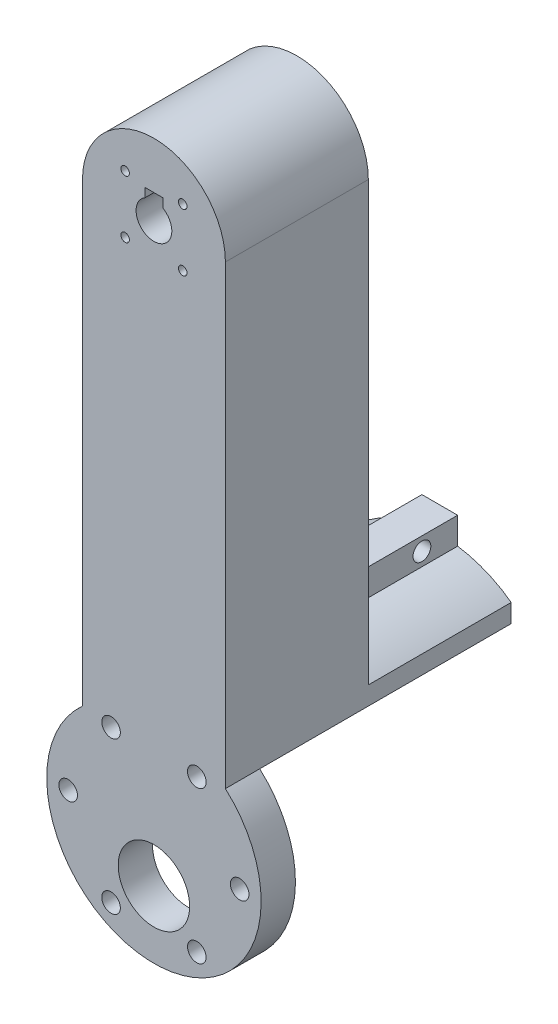
SolidWorks part; units mm, degrees
ref_plane "Front Plane" through (0, 0, 0) normal (0, 0, 1) x (1, 0, 0)
ref_plane "Top Plane" through (0, 0, 0) normal (0, 1, 0) x (1, 0, 0)
ref_plane "Right Plane" through (0, 0, 0) normal (1, 0, 0) x (0, 0, -1)
sketch "Sketch1" plane through (0, 0, 0) normal (0, 0, 1) x (1, 0, 0)
  line L0 (-5.1187, 55.9187) -> (5.1187, 45.6813) construction
  line L2 (12.7, 50.8) -> (12.7, -50.8)
  line L4 (-12.7, 50.8) -> (-12.7, -50.8)
  line L5 (12.7, 50.8) -> (-12.7, -50.8) construction
  line L6 (12.7, -50.8) -> (-12.7, 50.8) construction
  line L7 (5.1187, 55.9187) -> (-5.1187, 45.6813) construction
  line L8 (0, 50.8) -> (0, 51.7208) construction
  arc A0 (-12.7, 50.8) -> (12.7, 50.8) centre (0, 50.8) cw
  arc A1 (12.7, -50.8) -> (-12.7, -50.8) centre (0, -50.8) cw
  circle A2 centre (0, 50.8) radius 3.175
  circle A3 centre (-5.1187, 55.9187) radius 0.762
  circle A4 centre (5.1187, 55.9187) radius 0.762
  circle A5 centre (5.1187, 45.6813) radius 0.762
  circle A6 centre (-5.1187, 45.6813) radius 0.762
  point P0 (0, 0)
  point P14 (0, 50.8)
  point P15 (0, 50.8)
  point P20 (0, 0)
  point P21 (0, 51.7208)
  dimension "D3" = 6.35
  dimension "D6" = 1.524
  dimension "D1" = 25.4
  dimension "D2" = 101.6
  dimension "D4" = 45
  dimension "D5" = 14.478
extrude "Boss-Extrude1" add sketch "Sketch1" along normal blind 25.4
sketch "Sketch2" plane through (0, 0, 0) normal (0, 0, -1) x (-1, 0, 0)
  circle A0 centre (0, -44.45) radius 19.05
  arc A2 (-12.7, -50.8) -> (12.7, -50.8) centre (0, -50.8) ccw construction
  point P5 (0, 0)
  dimension "D1" = 38.1
extrude "Boss-Extrude2" add sketch "Sketch2" against normal blind 25.4
sketch "Sketch4" plane through (0, 0, 25.4) normal (0, 0, 1) x (1, 0, 0)
  circle A0 centre (0, -44.45) radius 19.05
  arc A1 (-12.7, -30.251) -> (12.7, -30.251) centre (0, -44.45) ccw construction
  point P5 (0, 0)
  point P6 (0, 0)
  point P7 (0, 0)
  point P8 (0, 0)
  point P9 (0, 0)
  dimension "D1" = 38.1
sketch "Sketch3" plane through (0, 0, 25.4) normal (0, 0, 1) x (1, 0, 0)
  line L0 (-15.24, -44.45) -> (15.24, -44.45) construction
  line L1 (15.24, -44.45) -> (7.62, -30.9593) construction
  line L2 (-15.24, -44.45) -> (-7.62, -30.9593) construction
  line L3 (-15.24, -44.45) -> (-7.62, -57.9407) construction
  line L4 (15.24, -44.45) -> (7.62, -57.9407) construction
  circle A0 centre (-7.62, -30.9593) radius 1.651
  circle A1 centre (7.62, -30.9593) radius 1.651
  circle A2 centre (-15.24, -44.45) radius 1.651
  circle A3 centre (-7.62, -57.9407) radius 1.651
  circle A4 centre (7.62, -57.9407) radius 1.651
  circle A5 centre (15.24, -44.45) radius 1.651
  point P10 (0, -44.45)
  dimension "D5" = 3.302
  dimension "D1" = 30.48
  dimension "D2" = 15.494
  dimension "D3" = 30.988
  dimension "D4" = 15.24
extrude "Cut-Extrude1" cut sketch "Sketch3" against normal blind 25.4
sketch "Sketch5" plane through (0, 0, 25.4) normal (0, 0, 1) x (1, 0, 0)
  circle A0 centre (0, -51.562) radius 6.35
  point P2 (0, -51.562)
  point P4 (0, 0)
  dimension "D1" = 12.7
  dimension "D2" = 7.112
extrude "Cut-Extrude2" cut sketch "Sketch5" against normal blind 25.4
sketch "Sketch6" plane through (0, 0, 0) normal (0, 0, -1) x (-1, 0, 0)
  line L1 (-1.5875, 55.1371) -> (1.5875, 55.1371)
  line L2 (-1.5875, 55.1371) -> (-1.5875, 53.5496)
  line L3 (-1.5875, 53.5496) -> (1.5875, 53.5496)
  line L4 (1.5875, 55.1371) -> (1.5875, 53.5496)
  circle A0 centre (0, 50.8) radius 3.175 construction
  point P4 (0, 0)
  point P7 (0, 0)
  dimension "D1" = 3.175
  dimension "D2" = 1.5875
extrude "Cut-Extrude3" cut sketch "Sketch6" against normal blind 25.4
sketch "Sketch8" plane through (0, 0, 0) normal (0, 0, -1) x (-1, 0, 0)
  circle A0 centre (0, -44.45) radius 19.05
  dimension "D1" = 38.1
extrude "Cut-Extrude4" cut sketch "Sketch8" against normal blind 19.3
sketch "Sketch9" plane through (0, 0, 0) normal (0, 0, -1) x (-1, 0, 0)
  line L0 (12.7, 50.8) -> (12.7, -30.251) construction
  line L1 (-12.7, -30.251) -> (-12.7, 50.8) construction
  line L2 (-12.7, -30.251) -> (-12.7, -26.9904)
  line L3 (12.7, -30.251) -> (12.7, -26.9904)
  arc A0 (-12.7, -30.251) -> (12.7, -30.251) centre (0, -44.45) cw
  arc A1 (-12.7, -26.9904) -> (12.7, -26.9904) centre (0, -44.45) cw
  dimension "D1" = 2.54
extrude "Boss-Extrude3" add sketch "Sketch9" along normal blind 25.4
sketch "Sketch10" plane through (0, 0, 0) normal (0, 0, -1) x (-1, 0, 0)
  line L1 (-3.175, -18.3322) -> (3.175, -18.3322)
  line L2 (-3.175, -18.3322) -> (-3.175, -23.0947)
  line L3 (-3.175, -23.0947) -> (3.175, -23.0947)
  line L4 (3.175, -18.3322) -> (3.175, -23.0947)
  arc A0 (12.7, -26.9904) -> (-12.7, -26.9904) centre (0, -44.45) ccw construction
  point P4 (0, -18.3322)
  point P6 (0, 0)
  dimension "D1" = 6.35
  dimension "D2" = 4.7625
extrude "Boss-Extrude4" add sketch "Sketch10" along normal up to surface (25.4 mm away) up to face at (0, -26.3753, -25.4)
sketch "Sketch11" plane through (3.175, 0, 0) normal (1, 0, 0) x (0, 0, -1)
  line L0 (24.0343, -18.3322) -> (24.0343, -23.0947) construction
  line L1 (25.4, -18.3322) -> (0, -18.3322) construction
  line L2 (25.4, -23.0947) -> (0, -23.0947) construction
  line L3 (0, -26.9904) -> (0, 50.8) construction
  line L4 (25.4, -23.0947) -> (25.4, -18.3322) construction
  circle A0 centre (6.35, -20.7135) radius 1.5875
  circle A1 centre (19.05, -20.7135) radius 1.5875
  point P8 (5.442, -20.7135)
  point P9 (24.0343, -20.7135)
  point P16 (19.05, -20.7135)
  point P17 (0, 0)
  dimension "D1" = 3.175
  dimension "D2" = 6.35
  dimension "D3" = 6.35
extrude "Cut-Extrude5" cut sketch "Sketch11" against normal through all
